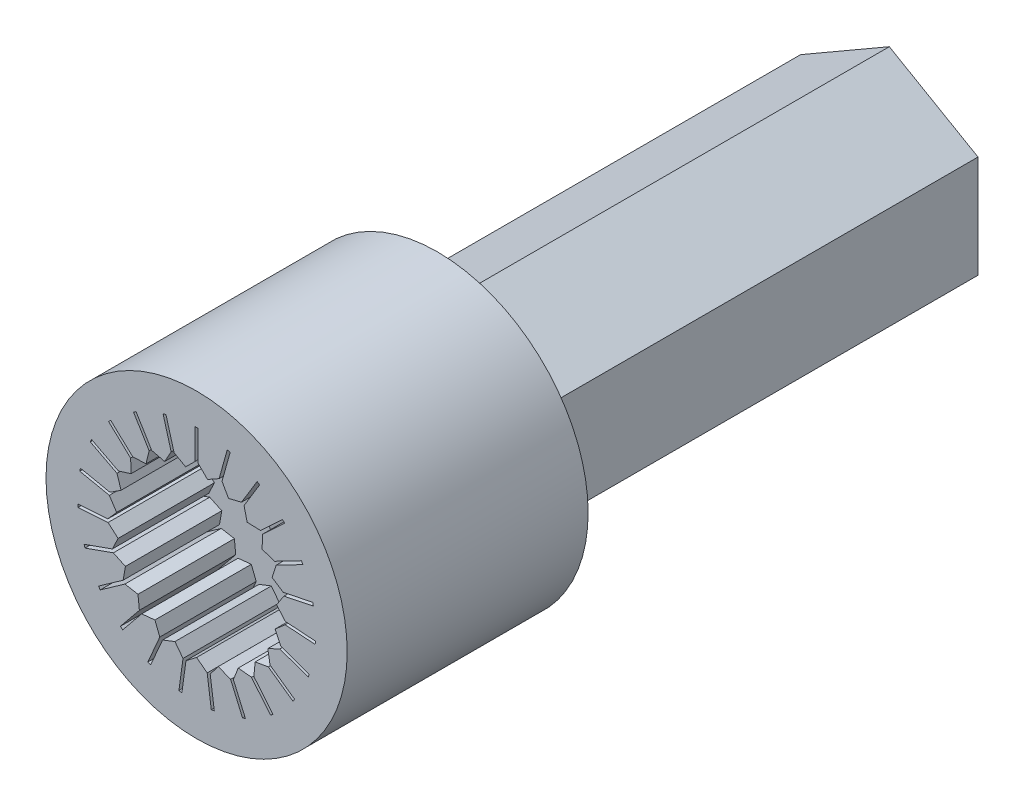
SolidWorks part; units mm, degrees
ref_plane "正面" through (0, 0, 0) normal (0, 0, 1) x (1, 0, 0)
ref_plane "平面" through (0, 0, 0) normal (0, 1, 0) x (1, 0, 0)
ref_plane "右側面" through (0, 0, 0) normal (1, 0, 0) x (0, 0, -1)
sketch "ｽｹｯﾁ1" plane through (0, 0, 0) normal (0, 0, 1) x (1, 0, 0)
  line L1 (0, 3.4) -> (-2.9445, 1.7)
  line L2 (-2.9445, 1.7) -> (-2.9445, -1.7)
  line L3 (-2.9445, -1.7) -> (0, -3.4)
  line L4 (0, -3.4) -> (2.9445, -1.7)
  line L5 (2.9445, -1.7) -> (2.9445, 1.7)
  line L6 (2.9445, 1.7) -> (0, 3.4)
  circle A0 centre (0, 0) radius 2.9445 construction
  dimension "D1" = 6.8
extrude "ﾎﾞｽ - 押し出し1" add sketch "ｽｹｯﾁ1" along normal blind 15
sketch "ｽｹｯﾁ6" plane through (0, 0, 15) normal (0, 0, 1) x (1, 0, 0)
  circle A0 centre (0, 0) radius 5
  dimension "D1" = 10
extrude "ﾎﾞｽ - 押し出し3" add sketch "ｽｹｯﾁ6" along normal blind 8
sketch "ｽｹｯﾁ5" plane through (0, 0, 23) normal (0, 0, 1) x (1, 0, 0)
  line L0 (-0.3625, 2.6375) -> (0, 3) construction
  line L1 (0, 3) -> (0.3625, 2.6375) construction
  line L2 (-0.3625, 2.6375) -> (0, 0) construction
  line L3 (0, 0) -> (0.3625, 2.6375) construction
  line L4 (0, 3) -> (0, 0) construction
  line L5 (-0.05, 2.95) -> (-0.05, 3.95)
  line L6 (-0.05, 3.95) -> (0.05, 3.95)
  line L7 (0.05, 3.95) -> (0.05, 2.95)
  line L8 (-0.05, 2.95) -> (0.05, 2.95) construction
  line L9 (-0.3625, 2.6375) -> (-0.05, 2.95)
  line L10 (-0.05, 2.95) -> (0.05, 2.95) construction
  line L11 (0.3625, 2.6375) -> (0.05, 2.95)
  line L12 (0.3625, 2.6375) -> (0.7478, 2.8541)
  line L13 (0.7478, 2.8541) -> (1.0176, 3.817)
  line L14 (1.1138, 3.79) -> (0.844, 2.8271)
  line L15 (1.0607, 2.4419) -> (0.844, 2.8271)
  line L16 (1.0176, 3.817) -> (1.1138, 3.79)
  line L17 (1.0607, 2.4419) -> (1.4901, 2.5465)
  line L18 (1.4901, 2.5465) -> (2.0096, 3.4009)
  line L19 (2.0951, 3.349) -> (1.5755, 2.4946)
  line L20 (1.6801, 2.0652) -> (1.5755, 2.4946)
  line L21 (2.0096, 3.4009) -> (2.0951, 3.349)
  line L22 (1.6801, 2.0652) -> (2.1218, 2.0501)
  line L23 (2.1218, 2.0501) -> (2.8527, 2.7326)
  line L24 (2.9209, 2.6595) -> (2.1901, 1.977)
  line L25 (2.175, 1.5353) -> (2.1901, 1.977)
  line L26 (2.8527, 2.7326) -> (2.9209, 2.6595)
  line L27 (2.175, 1.5353) -> (2.5963, 1.4016)
  line L28 (2.5963, 1.4016) -> (3.4841, 1.8617)
  line L29 (3.5301, 1.7729) -> (2.6423, 1.3128)
  line L30 (2.5086, 0.8915) -> (2.6423, 1.3128)
  line L31 (3.4841, 1.8617) -> (3.5301, 1.7729)
  line L32 (2.5086, 0.8915) -> (2.8781, 0.6491)
  line L33 (2.8781, 0.6491) -> (3.8572, 0.8526)
  line L34 (3.8776, 0.7547) -> (2.8985, 0.5512)
  line L35 (2.6561, 0.1817) -> (2.8985, 0.5512)
  line L36 (3.8572, 0.8526) -> (3.8776, 0.7547)
  line L37 (2.6561, 0.1817) -> (2.9465, -0.1514)
  line L38 (2.9465, -0.1514) -> (3.9442, -0.2197)
  line L39 (3.9374, -0.3194) -> (2.9397, -0.2512)
  line L40 (2.6066, -0.5417) -> (2.9397, -0.2512)
  line L41 (3.9442, -0.2197) -> (3.9374, -0.3194)
  line L42 (2.6066, -0.5417) -> (2.7964, -0.9408)
  line L43 (2.7964, -0.9408) -> (3.7387, -1.2757)
  line L44 (3.7052, -1.3699) -> (2.7629, -1.035)
  line L45 (2.3638, -1.2248) -> (2.7629, -1.035)
  line L46 (3.7387, -1.2757) -> (3.7052, -1.3699)
  line L47 (2.3638, -1.2248) -> (2.4389, -1.6604)
  line L48 (2.4389, -1.6604) -> (3.2559, -2.237)
  line L49 (3.1982, -2.3187) -> (2.3812, -1.7421)
  line L50 (1.9457, -1.8171) -> (2.3812, -1.7421)
  line L51 (3.2559, -2.237) -> (3.1982, -2.3187)
  line L52 (1.9457, -1.8171) -> (1.9005, -2.2568)
  line L53 (1.9005, -2.2568) -> (2.5316, -3.0325)
  line L54 (2.454, -3.0956) -> (1.8229, -2.3199)
  line L55 (1.3833, -2.2747) -> (1.8229, -2.3199)
  line L56 (2.5316, -3.0325) -> (2.454, -3.0956)
  line L57 (1.3833, -2.2747) -> (1.2211, -2.6859)
  line L58 (1.2211, -2.6859) -> (1.6195, -3.6031)
  line L59 (1.5278, -3.6429) -> (1.1294, -2.7257)
  line L60 (0.7183, -2.5636) -> (1.1294, -2.7257)
  line L61 (1.6195, -3.6031) -> (1.5278, -3.6429)
  line L62 (0.7183, -2.5636) -> (0.4512, -2.9157)
  line L63 (0.4512, -2.9157) -> (0.5874, -3.9064)
  line L64 (0.4883, -3.92) -> (0.3522, -2.9293)
  line L65 (0, -2.6623) -> (0.3522, -2.9293)
  line L66 (0.5874, -3.9064) -> (0.4883, -3.92)
  line L67 (0, -2.6623) -> (-0.3522, -2.9293)
  line L68 (-0.3522, -2.9293) -> (-0.4883, -3.92)
  line L69 (-0.5874, -3.9064) -> (-0.4512, -2.9157)
  line L70 (-0.7183, -2.5636) -> (-0.4512, -2.9157)
  line L71 (-0.4883, -3.92) -> (-0.5874, -3.9064)
  line L72 (-0.7183, -2.5636) -> (-1.1294, -2.7257)
  line L73 (-1.1294, -2.7257) -> (-1.5278, -3.6429)
  line L74 (-1.6195, -3.6031) -> (-1.2211, -2.6859)
  line L75 (-1.3833, -2.2747) -> (-1.2211, -2.6859)
  line L76 (-1.5278, -3.6429) -> (-1.6195, -3.6031)
  line L77 (-1.3833, -2.2747) -> (-1.8229, -2.3199)
  line L78 (-1.8229, -2.3199) -> (-2.454, -3.0956)
  line L79 (-2.5316, -3.0325) -> (-1.9005, -2.2568)
  line L80 (-1.9457, -1.8171) -> (-1.9005, -2.2568)
  line L81 (-2.454, -3.0956) -> (-2.5316, -3.0325)
  line L82 (-1.9457, -1.8171) -> (-2.3812, -1.7421)
  line L83 (-2.3812, -1.7421) -> (-3.1982, -2.3187)
  line L84 (-3.2559, -2.237) -> (-2.4389, -1.6604)
  line L85 (-2.3638, -1.2248) -> (-2.4389, -1.6604)
  line L86 (-3.1982, -2.3187) -> (-3.2559, -2.237)
  line L87 (-2.3638, -1.2248) -> (-2.7629, -1.035)
  line L88 (-2.7629, -1.035) -> (-3.7052, -1.3699)
  line L89 (-3.7387, -1.2757) -> (-2.7964, -0.9408)
  line L90 (-2.6066, -0.5417) -> (-2.7964, -0.9408)
  line L91 (-3.7052, -1.3699) -> (-3.7387, -1.2757)
  line L92 (-2.6066, -0.5417) -> (-2.9397, -0.2512)
  line L93 (-2.9397, -0.2512) -> (-3.9374, -0.3194)
  line L94 (-3.9442, -0.2197) -> (-2.9465, -0.1514)
  line L95 (-2.6561, 0.1817) -> (-2.9465, -0.1514)
  line L96 (-3.9374, -0.3194) -> (-3.9442, -0.2197)
  line L97 (-2.6561, 0.1817) -> (-2.8985, 0.5512)
  line L98 (-2.8985, 0.5512) -> (-3.8776, 0.7547)
  line L99 (-3.8572, 0.8526) -> (-2.8781, 0.6491)
  line L100 (-2.5086, 0.8915) -> (-2.8781, 0.6491)
  line L101 (-3.8776, 0.7547) -> (-3.8572, 0.8526)
  line L102 (-2.5086, 0.8915) -> (-2.6423, 1.3128)
  line L103 (-2.6423, 1.3128) -> (-3.5301, 1.7729)
  line L104 (-3.4841, 1.8617) -> (-2.5963, 1.4016)
  line L105 (-2.175, 1.5353) -> (-2.5963, 1.4016)
  line L106 (-3.5301, 1.7729) -> (-3.4841, 1.8617)
  line L107 (-2.175, 1.5353) -> (-2.1901, 1.977)
  line L108 (-2.1901, 1.977) -> (-2.9209, 2.6595)
  line L109 (-2.8527, 2.7326) -> (-2.1218, 2.0501)
  line L110 (-1.6801, 2.0652) -> (-2.1218, 2.0501)
  line L111 (-2.9209, 2.6595) -> (-2.8527, 2.7326)
  line L112 (-1.6801, 2.0652) -> (-1.5755, 2.4946)
  line L113 (-1.5755, 2.4946) -> (-2.0951, 3.349)
  line L114 (-2.0096, 3.4009) -> (-1.4901, 2.5465)
  line L115 (-1.0607, 2.4419) -> (-1.4901, 2.5465)
  line L116 (-2.0951, 3.349) -> (-2.0096, 3.4009)
  line L117 (-1.0607, 2.4419) -> (-0.844, 2.8271)
  line L118 (-0.844, 2.8271) -> (-1.1138, 3.79)
  line L119 (-1.0176, 3.817) -> (-0.7478, 2.8541)
  line L120 (-0.3625, 2.6375) -> (-0.7478, 2.8541)
  line L121 (-1.1138, 3.79) -> (-1.0176, 3.817)
  circle A0 centre (0, 0) radius 3 construction
  circle A1 centre (0, 0) radius 2.6623 construction
  point P147 (0, 0)
  dimension "D1" = 6
  dimension "D2" = 7.826
  dimension "D3" = 7.826
  dimension "D4" = 0.1
  dimension "D5" = 1
  dimension "D6" = 23
extrude "ｶｯﾄ - 押し出し5" cut sketch "ｽｹｯﾁ5" against normal blind 3.2
chamfer "面取り1" distance 1 angle 45 6 edges at (1.4722, 2.55, 15) (2.9445, 0, 15) (1.4722, -2.55, 15) (-1.4722, -2.55, 15) (-2.9445, 0, 15) (-1.4722, 2.55, 15)
sketch "ｽｹｯﾁ7" plane through (0, 0, 0) normal (0, 0, -1) x (-1, 0, 0)
  line L1 (1.3, 0) -> (0.65, 1.1258)
  line L2 (0.65, 1.1258) -> (-0.65, 1.1258)
  line L3 (-0.65, 1.1258) -> (-1.3, 0)
  line L4 (-1.3, 0) -> (-0.65, -1.1258)
  line L5 (-0.65, -1.1258) -> (0.65, -1.1258)
  line L6 (0.65, -1.1258) -> (1.3, 0)
  circle A0 centre (0, 0) radius 1.1258 construction
  point P1 (0, 0)
  dimension "D1" = 2.6
extrude "ｶｯﾄ - 押し出し6" cut sketch "ｽｹｯﾁ7" against normal through all
equation "\"18.4.300mm\"=18.3"
equation "\"D2@ｽｹｯﾁ5\"=360deg/46"
equation "\"D3@ｽｹｯﾁ5\"=\"D2@ｽｹｯﾁ5\""
